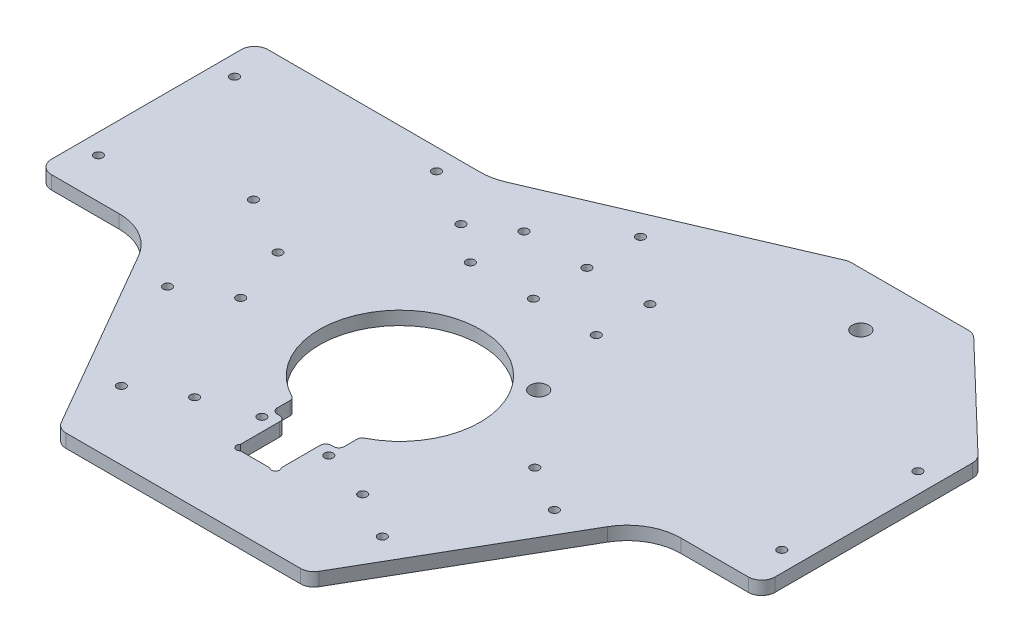
SolidWorks part; units mm, degrees
material "Acrylic (Medium-high impact)"
ref_plane "Front Plane" through (0, 0, 0) normal (0, 0, 1) x (1, 0, 0)
ref_plane "Top Plane" through (0, 0, 0) normal (0, 1, 0) x (1, 0, 0)
ref_plane "Right Plane" through (0, 0, 0) normal (1, 0, 0) x (0, 0, -1)
sketch "Sketch1" plane through (0, 0, 0) normal (0, 1, 0) x (1, 0, 0)
  line L0 (0, 0) -> (0, 59.7887) construction
  line L1 (88.7366, -45.4586) -> (19.8205, -5.6699) construction
  line L2 (-5, 99.5775) -> (5, 99.5775) construction
  line L3 (-5, 99.5775) -> (-5, 20) construction
  line L4 (-5, 20) -> (5, 20) construction
  line L5 (5, 99.5775) -> (5, 20) construction
  line L6 (-5, 99.5775) -> (5, 20) construction
  line L7 (-5, 20) -> (5, 99.5775) construction
  line L8 (88.7366, -45.4586) -> (83.7366, -54.1189) construction
  line L9 (83.7366, -54.1189) -> (14.8205, -14.3301) construction
  line L10 (19.8205, -5.6699) -> (14.8205, -14.3301) construction
  line L11 (-83.7366, -54.1189) -> (-14.8205, -14.3301) construction
  line L12 (-83.7366, -54.1189) -> (-88.7366, -45.4586) construction
  line L13 (-88.7366, -45.4586) -> (-19.8205, -5.6699) construction
  line L14 (-14.8205, -14.3301) -> (-19.8205, -5.6699) construction
  line L15 (-5, 59.7887) -> (-120, 59.7887) construction
  line L16 (-49.2786, -34.2245) -> (8.2214, -133.8174) construction
  line L23 (54.2786, -25.5642) -> (111.7786, 74.0287) construction
  circle A0 centre (0, 0) radius 20 construction
  circle A1 centre (-12.5, -19.3067) radius 3 construction
  circle A2 centre (12.5, -19.3067) radius 3 construction
  point P19 (0, 0)
  dimension "D1" = 40
  dimension "D6" = 6
  dimension "D7" = 25
  dimension "D2" = 79.5775
  dimension "D3" = 10
  dimension "D5" = 115
  dimension "D4" = 3
sketch "Sketch2" plane through (0, 0, 0) normal (0, 1, 0) x (1, 0, 0)
  line L0 (-5, 20) -> (5, 99.5775) construction
  line L1 (-23.5, 49.7887) -> (23.5, 49.7887) construction
  line L2 (-23.5, 49.7887) -> (-23.5, 69.7887) construction
  line L3 (-23.5, 69.7887) -> (23.5, 69.7887) construction
  line L4 (23.5, 49.7887) -> (23.5, 69.7887) construction
  line L5 (-23.5, 49.7887) -> (23.5, 69.7887) construction
  line L6 (-23.5, 69.7887) -> (23.5, 49.7887) construction
  line L8 (46.6434, 80.7887) -> (-46.6434, 80.7887)
  line L9 (-46.6434, 80.7887) -> (-93.2868, 0)
  line L10 (-93.2868, 0) -> (-46.6434, -80.7887)
  line L11 (-46.6434, -80.7887) -> (46.6434, -80.7887)
  line L12 (46.6434, -80.7887) -> (93.2868, 0)
  line L13 (93.2868, 0) -> (46.6434, 80.7887)
  circle A0 centre (23.5, 69.7887) radius 1.6
  circle A1 centre (23.5, 49.7887) radius 1.6
  circle A2 centre (-23.5, 49.7887) radius 1.6
  circle A3 centre (-23.5, 69.7887) radius 1.6
  circle A4 centre (0, 0) radius 30
  circle A5 centre (0, 0) radius 80.7887 construction
  circle A6 centre (54.8683, -4.5428) radius 1.6
  circle A7 centre (72.1888, -14.5428) radius 1.6
  circle A8 centre (48.6888, -55.246) radius 1.6
  circle A9 centre (31.3683, -45.246) radius 1.6
  circle A10 centre (-31.3683, -45.246) radius 1.6
  circle A11 centre (-48.6888, -55.246) radius 1.6
  circle A12 centre (-72.1888, -14.5428) radius 1.6
  circle A13 centre (-54.8683, -4.5428) radius 1.6
  point P0 (0, 59.7887)
  point P39 (0, 0)
  dimension "D3" = 3.2
  dimension "D4" = 60
  dimension "D5" = 11
  dimension "D1" = 47
  dimension "D2" = 20
  dimension "D6" = 3
extrude "Boss-Extrude1" add sketch "Sketch2" along normal blind 5
sketch "Sketch3" plane through (0, 0, 0) normal (0, 1, 0) x (1, 0, 0)
  line L0 (18, 80.7887) -> (18, 24) construction
  line L1 (46.6434, 80.7887) -> (-46.6434, 80.7887) construction
  line L2 (5, 99.5775) -> (5, 20) construction
  line L3 (85.9256, 92.2887) -> (41.3253, 15.0387) construction
  line L5 (23.5, 49.7887) -> (30.5, 49.7887) construction
  line L6 (30.5, 33.7887) -> (30.5, 49.7887) construction
  line L8 (46.6434, 120.7887) -> (93.2868, 120.7887)
  line L9 (93.2868, 120.7887) -> (93.2868, 0)
  line L14 (93.2868, 0) -> (46.6434, 80.7887) construction
  line L15 (93.2868, 0) -> (46.6434, 80.7887)
  line L16 (-46.6434, 80.7887) -> (46.6434, 120.7887)
  line L17 (46.6434, 120.7887) -> (46.6434, 80.7887) construction
  line L18 (46.6434, 80.7887) -> (-46.6434, 80.7887)
  line L19 (46.6434, -80.7887) -> (93.2868, 0) construction
  circle A0 centre (0, 0) radius 30 construction
  circle A1 centre (30.5, 21.2887) radius 12.5 construction
  circle A5 centre (71.2032, 100.7887) radius 3.2
  circle A6 centre (71.2032, 100.7887) radius 20 construction
  circle A7 centre (71.2032, 100.7887) radius 17 construction
  point P19 (85.9256, 92.2887)
  point P32 (69.9651, 120.7887)
  dimension "D2" = 25
  dimension "D3" = 16
  dimension "D4" = 6.4
  dimension "D5" = 20
  dimension "D6" = 34
  dimension "D1" = 13
extrude "Boss-Extrude2" add sketch "Sketch3" along normal up to surface (5 mm away) up to face at (-31.3683, 5, 46.846)
sketch "Sketch4" plane through (0, 5, 0) normal (0, 1, 0) x (1, 0, 0)
  circle A0 centre (30.5, 21.2887) radius 3.2
  dimension "D1" = 6.4
extrude "Cut-Extrude1" cut sketch "Sketch4" against normal through all
sketch "Sketch5" plane through (0, 5, 0) normal (0, 1, 0) x (1, 0, 0)
  line L4 (-7.6, -29.0214) -> (7.6, -29.0214)
  line L5 (-7.6, -29.0214) -> (-7.6, -54.0214)
  line L6 (-7.6, -54.0214) -> (7.6, -54.0214)
  line L7 (7.6, -29.0214) -> (7.6, -54.0214)
  circle A2 centre (0, 0) radius 30 construction
  dimension "D1" = 15.2
  dimension "D2" = 25
extrude "Cut-Extrude2" cut sketch "Sketch5" against normal through all
sketch "Sketch7" plane through (0, 0, 0) normal (0, -1, 0) x (1, 0, 0)
  line L0 (0, 0) -> (0, 39.0214) construction
  line L1 (0, 39.0214) -> (12.5, 39.0214) construction
  line L2 (0, 39.0214) -> (-12.5, 39.0214) construction
  line L3 (-7.6, 52.9607) -> (-6.5393, 52.9607) construction
  line L4 (-7.6, 29.0214) -> (-7.6, 54.0214) construction
  line L5 (-6.5393, 52.9607) -> (-6.5393, 54.0214) construction
  line L6 (-7.6, 54.0214) -> (7.6, 54.0214) construction
  line L7 (6.5393, 54.0214) -> (6.5393, 52.9607) construction
  line L8 (6.5393, 52.9607) -> (7.6, 52.9607) construction
  line L9 (7.6, 54.0214) -> (7.6, 29.0214) construction
  line L11 (-12.5, 35.2718) -> (12.5, 35.2718)
  line L12 (-12.5, 35.2718) -> (-12.5, 27.2718)
  line L13 (-12.5, 27.2718) -> (12.5, 27.2718)
  line L14 (12.5, 35.2718) -> (12.5, 27.2718)
  line L15 (-12.5, 35.2718) -> (12.5, 27.2718) construction
  line L16 (-12.5, 27.2718) -> (12.5, 35.2718) construction
  circle A0 centre (-12.5, 39.0214) radius 1.6
  circle A1 centre (12.5, 39.0214) radius 1.6
  circle A2 centre (-6.5393, 52.9607) radius 1.5
  circle A3 centre (6.5393, 52.9607) radius 1.5
  arc A4 (-7.6, 29.0214) -> (7.6, 29.0214) centre (0, 0) ccw construction
  point P24 (0, 31.2718)
  point P31 (11.6751, 33.6595)
  point P32 (12.5, 34.4337)
  dimension "D1" = 25
  dimension "D3" = 3.2
  dimension "D4" = 3
  dimension "D2" = 39.0214
  dimension "D5" = 25
  dimension "D6" = 8
extrude "Cut-Extrude3" cut sketch "Sketch7" against normal through all
sketch "Sketch8" plane through (0, 0, 0) normal (0, 1, 0) x (1, 0, 0)
  line L0 (-93.2868, 0) -> (-135, 0)
  line L1 (-135, 0) -> (-135, 80.7887)
  line L2 (-135, 80.7887) -> (-46.6434, 80.7887)
  line L3 (-93.2868, 0) -> (-46.6434, 80.7887)
  line L4 (93.2868, 0) -> (135, 0)
  line L5 (135, 0) -> (135, 80.7887)
  line L6 (135, 80.7887) -> (93.2868, 120.7887)
  line L7 (93.2868, 0) -> (93.2868, 120.7887)
  dimension "D1" = 270
extrude "Boss-Extrude3" add sketch "Sketch8" along normal up to surface (5 mm away) up to face at (12.5, 5, 37.4214)
sketch "Sketch9" plane through (0, 0, 0) normal (0, -1, 0) x (1, 0, 0)
  line L0 (135, 0) -> (135, -80.7887) construction
  circle A0 centre (-37.6014, -60.3916) radius 1.6
  circle A1 centre (-59.252, -72.8916) radius 1.6
  circle A2 centre (-84.252, -29.5904) radius 1.6
  circle A3 centre (-62.6014, -17.0904) radius 1.6
  circle A4 centre (0, -49.7887) radius 1.6
  circle A5 centre (0, -69.7887) radius 1.6
  circle A6 centre (0, -89.7887) radius 1.6
  circle A7 centre (127.5, -65.79) radius 1.6
  circle A8 centre (127.5, -15) radius 1.6
  circle A9 centre (-127.5, -14.9987) radius 1.6
  circle A10 centre (-127.5, -65.7887) radius 1.6
  dimension "D1" = 3.2
  dimension "D2" = 7.5
  dimension "D3" = 135
  dimension "D4" = 172.6014
  dimension "D5" = 194.252
  dimension "D6" = 197.6014
  dimension "D7" = 219.252
  dimension "D8" = 262.5
  dimension "D9" = 95.7875
  dimension "D10" = 95.7887
  dimension "D11" = 97.8791
  dimension "D12" = 110.3791
  dimension "D13" = 130.5775
  dimension "D14" = 141.1804
  dimension "D15" = 146.5775
  dimension "D16" = 146.5787
  dimension "D17" = 150.5775
  dimension "D18" = 153.6804
  dimension "D19" = 170.5775
extrude "Cut-Extrude4" cut sketch "Sketch9" against normal through all
fillet "Fillet1" radius 5 8 edges at (46.6434, 2.5, 80.7887) (-46.6434, 2.5, 80.7887) (-135, 2.5, -80.7887) (46.6434, 2.5, -120.7887) (93.2868, 2.5, -120.7887) (135, 2.5, -80.7887) (135, 2.5, 0) (-135, 2.5, 0)
fillet "Fillet2" radius 20 3 edges at (-46.6434, 2.5, -80.7887) (93.2868, 2.5, 0) (-93.2868, 2.5, 0)
fillet "Fillet3" radius 2 6 edges at (12.5, 2.5, 27.2718) (12.5, 2.5, 35.2718) (7.6, 2.5, 35.2718) (-7.6, 2.5, 35.2718) (-12.5, 2.5, 35.2718) (-12.5, 2.5, 27.2718)
